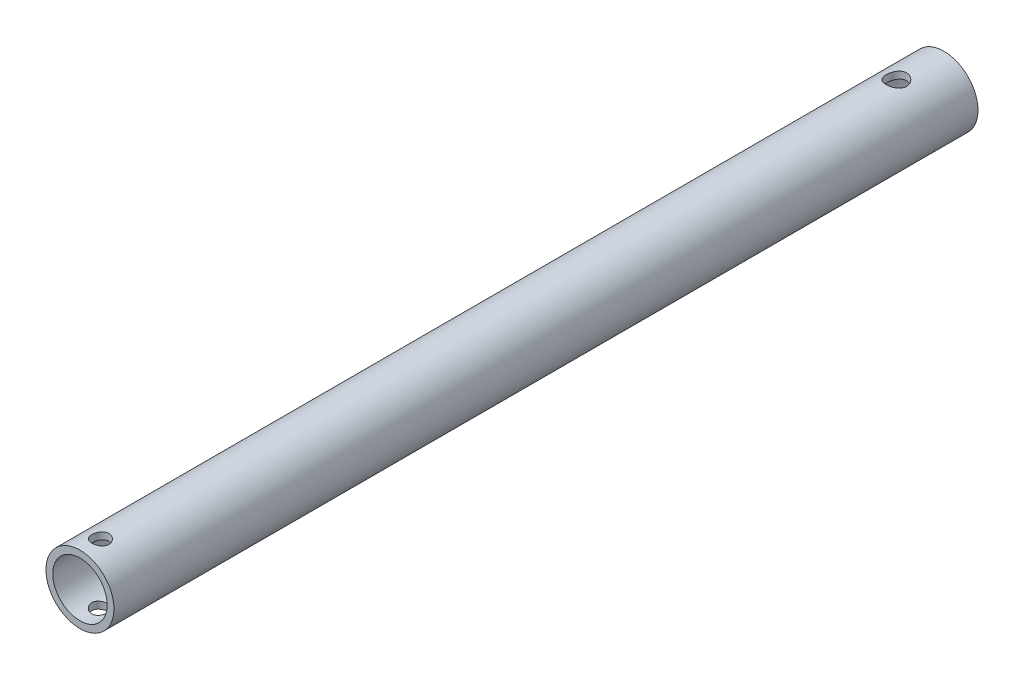
SolidWorks part; units mm, degrees
other "Markup1"
sketch "Sketch6" plane through (15.875, 15.875, -457.2) normal (0.0003, 1, -0.0035) x (0.9116, 0.0012, 0.411)
ref_plane "Front Plane" through (0, 0, 0) normal (0, 0, 1) x (1, 0, 0)
ref_plane "Top Plane" through (0, 0, 0) normal (0, 1, 0) x (1, 0, 0)
ref_plane "Right Plane" through (0, 0, 0) normal (1, 0, 0) x (0, 0, -1)
sketch "Sketch1" plane through (0, 0, 0) normal (0, 0, 1) x (1, 0, 0)
  line L0 (-15.875, 0) -> (15.875, 0) construction
  line L1 (0, -15.875) -> (0, 15.875) construction
  circle A0 centre (0, 0) radius 15.875
  circle A1 centre (0, 0) radius 12.7
  point P4 (0, 0)
  point P9 (0, 0)
  point P10 (12.7, 0)
  dimension "ID" = 25.4
  dimension "OD" = 31.75
  dimension "Wall Thickness" = 3.175
sketch "Sketch2" plane through (0, 0, 0) normal (1, 0, 0) x (0, 0, -1)
  line L0 (457.2, 15.875) -> (-457.2, 15.875) construction
  line L1 (0, 15.875) -> (0, -15.875) construction
  point P3 (-381, 15.875)
  point P4 (0, 15.875)
  point P5 (381, 15.875)
  dimension "D2" = 76.2
  dimension "Length" = 914.4
sketch "Sketch3" plane through (0, 0, 0) normal (0, 0, 1) x (1, 0, 0)
  line L0 (0, -15.875) -> (0, 15.875) construction
  circle A0 centre (0, 0) radius 15.875
  circle A1 centre (0, 0) radius 12.7
  circle A2 centre (0, 0) radius 12.7 construction
extrude "Boss-Extrude1" add sketch "Sketch3" along normal mid plane 914.4
sketch "Sketch4" plane through (0, 0, 457.2) normal (0, 0, 1) x (1, 0, 0)
  circle A0 centre (0, 0) radius 24.6875
extrude "Cut-Extrude1" cut sketch "Sketch4" against normal offset from surface (511.175 mm away) 403.225 up to face at (15.875, 0, -457.2)
sketch "Sketch5" plane through (0, 0, 0) normal (0, 1, 0) x (1, 0, 0)
  line L0 (-15.875, 53.975) -> (15.875, 53.975) construction
  line L1 (0, 63.5) -> (-15.875, 63.5) construction
  line L2 (-15.875, 457.2) -> (-15.875, 53.975) construction
  line L3 (0, 63.5) -> (15.875, 63.5) construction
  line L4 (15.875, 53.975) -> (15.875, 457.2) construction
  circle A0 centre (0, 63.5) radius 3.9687
  circle A1 centre (0, 434.975) radius 4.7625
  dimension "D1" = 7.9375
  dimension "D3" = 9.525
  dimension "D2" = 9.525
  dimension "D4" = 381
extrude "Cut-Extrude2" cut sketch "Sketch5" against normal through all both and the other way through all
equation "\"D1@Boss-Extrude1\" = \"Length@Sketch2\""
equation "\"D2@Sketch2\"=\"D1@Sketch2\""
